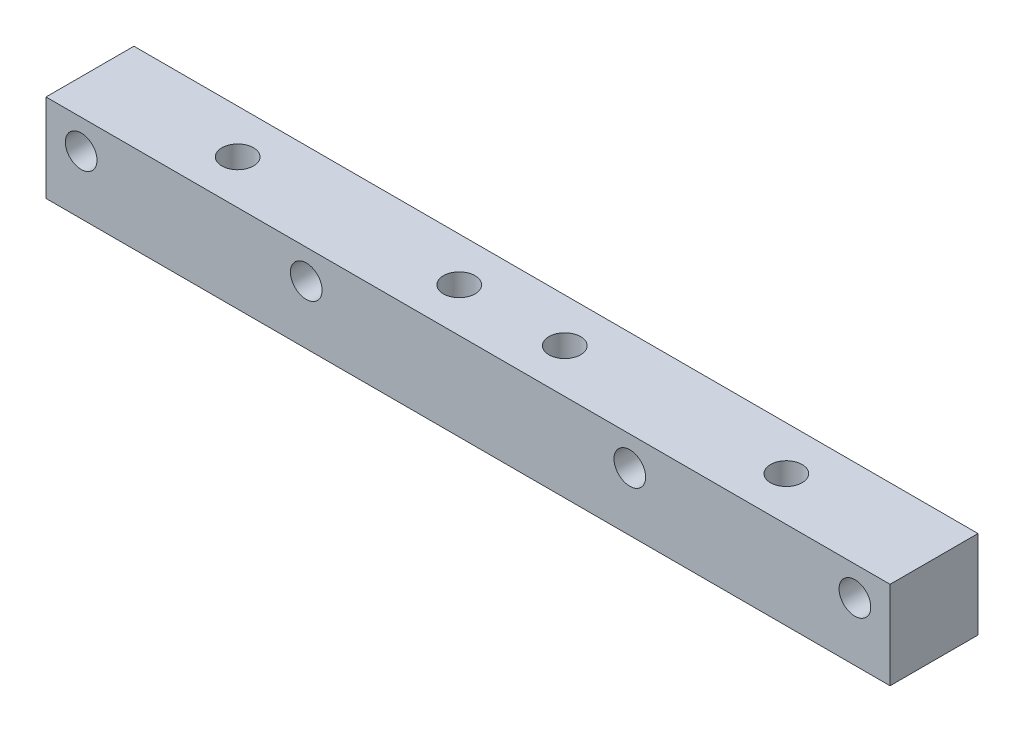
SolidWorks part; units mm, degrees
material "6061 Alloy"
ref_plane "Front Plane" through (0, 0, 0) normal (0, 0, 1) x (1, 0, 0)
ref_plane "Top Plane" through (0, 0, 0) normal (0, 1, 0) x (1, 0, 0)
ref_plane "Right Plane" through (0, 0, 0) normal (1, 0, 0) x (0, 0, -1)
sketch "Sketch1" plane through (0, 0, 0) normal (1, 0, 0) x (0, 0, -1)
  line L1 (-6.25, -6.25) -> (6.25, -6.25)
  line L2 (-6.25, -6.25) -> (-6.25, 6.25)
  line L3 (-6.25, 6.25) -> (6.25, 6.25)
  line L4 (6.25, -6.25) -> (6.25, 6.25)
  line L5 (-6.25, -6.25) -> (6.25, 6.25) construction
  line L6 (-6.25, 6.25) -> (6.25, -6.25) construction
  point P0 (0, 0)
  dimension "D1" = 12.5
extrude "Boss-Extrude1" add sketch "Sketch1" along normal mid plane 120
hole_wizard "Ø4.0mm Dowel Hole1" positions "Sketch2" profile "Sketch3" hole size "Ø4.0" standard "ANSI Metric" end condition through all
sketch "Sketch2" plane through (0, 0, 6.25) normal (0, 0, 1) x (1, 0, 0)
  line L0 (-55, 2.07) -> (-23, 2.07) construction
  line L1 (-23, 2.07) -> (23, 2.07) construction
  line L2 (23, 2.07) -> (55, 2.07) construction
  line L5 (-60, 6.25) -> (-60, -6.25) construction
  line L6 (60, -6.25) -> (-60, -6.25) construction
  line L7 (60, 6.25) -> (60, -6.25) construction
  point P0 (-55, 2.07)
  point P2 (-23, 2.07)
  point P4 (23, 2.07)
  point P6 (55, 2.07)
  dimension "D1" = 32
  dimension "D2" = 5
  dimension "D3" = 8.32
  dimension "D4" = 5
sketch "Sketch3" plane through (-55, 2.07, 6.25) normal (1, 0, 0) x (0, -1, 0)
  line L0 (0, 0) -> (0, 12.5)
  line L1 (0, 12.5) -> (2.25, 12.5)
  line L2 (2.25, 12.5) -> (2.25, 0)
  line L5 (2.25, 0) -> (0, 0)
  line L11 (0, -6.35) -> (0, 107.95) construction
  dimension "Thru Hole Dia." = 4.5
  dimension "Thru Hole Depth" = 12.5
hole_wizard "Ø1.0mm Dowel Hole1" positions "Sketch4" profile "Sketch5" hole size "Ø1.0" standard "ANSI Metric" end condition through all
sketch "Sketch4" plane through (0, 6.25, 0) normal (0, 1, 0) x (1, 0, 0)
  line L0 (-60, 6.25) -> (-60, -6.25) construction
  line L1 (60, 6.25) -> (60, -6.25) construction
  point P0 (-39, 0)
  point P5 (39, 0)
  point P14 (-7.5, 0)
  point P16 (7.5, 0)
  point P19 (12.7099, 0)
  dimension "D1" = 21
  dimension "D2" = 21
  dimension "D3" = 15
  dimension "D4" = 7.5
sketch "Sketch5" plane through (-39, 6.25, 0) normal (1, 0, 0) x (0, 0, 1)
  line L0 (0, 0) -> (0, 12.5)
  line L1 (0, 12.5) -> (2.25, 12.5)
  line L2 (2.25, 12.5) -> (2.25, 0)
  line L5 (2.25, 0) -> (0, 0)
  line L11 (0, -6.35) -> (0, 107.95) construction
  dimension "Thru Hole Dia." = 4.5
  dimension "Thru Hole Depth" = 12.5
equation "\"D1@Sketch4\"=(32/2)+5"
equation "\"D2@Sketch4\"=\"D1@Sketch4\""
equation "\"D4@Sketch4\"=\"D3@Sketch4\"/2"
